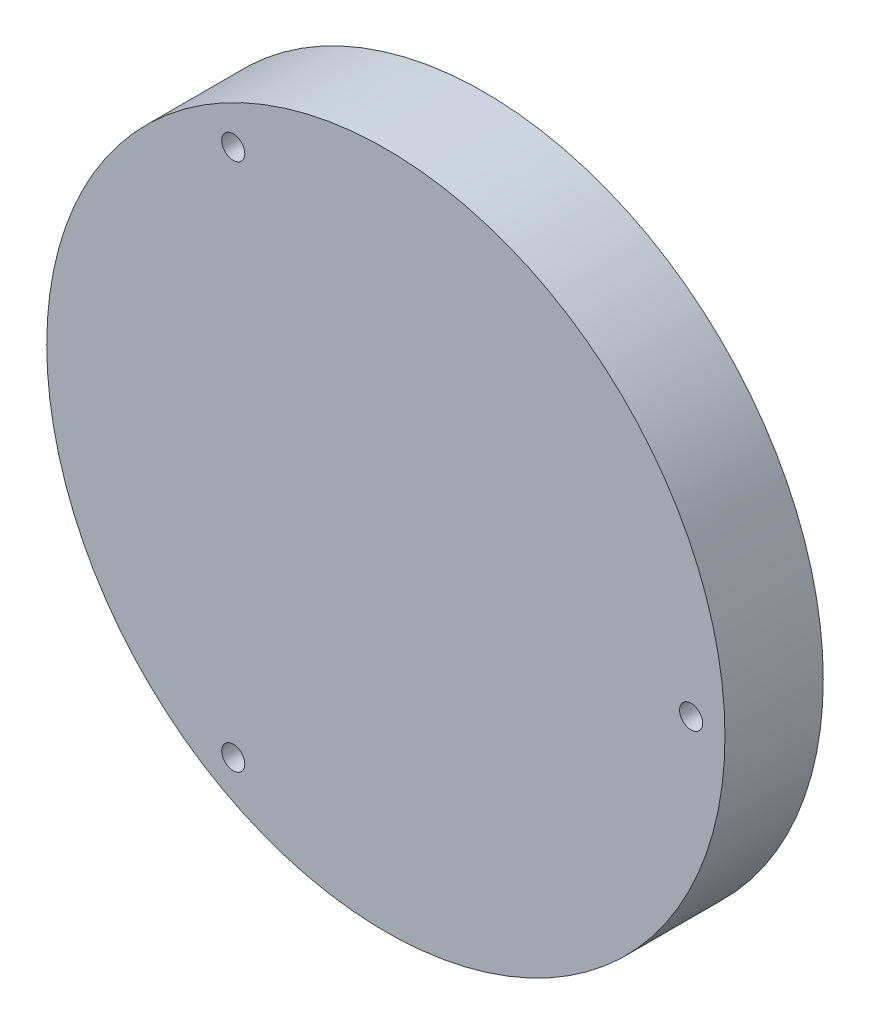
SolidWorks part; units mm, degrees
ref_plane "Front Plane" through (0, 0, 0) normal (1, 0, 0) x (0, 1, 0)
ref_plane "Top Plane" through (0, 0, 0) normal (0, 0, 1) x (0, 1, 0)
ref_plane "Right Plane" through (0, 0, 0) normal (0, 1, 0) x (-1, 0, 0)
sketch "Sketch2" plane through (0, 0, 0) normal (0, 0, 1) x (0, 1, 0)
  line L4 (0, -45) -> (38.9711, 22.5)
  line L5 (38.9711, 22.5) -> (-38.9711, 22.5)
  line L6 (-38.9711, 22.5) -> (0, -45)
  circle A2 centre (0, 0) radius 50
  circle A4 centre (0, 0) radius 22.5 construction
  circle A5 centre (-38.9711, 22.5) radius 1.7
  circle A6 centre (38.9711, 22.5) radius 1.7
  circle A7 centre (0, -45) radius 1.7
  dimension "D1" = 100
  dimension "D2" = 3.4
  dimension "D3" = 3.4
  dimension "D4" = 3.4
  dimension "D5" = 45
extrude "Boss-Extrude1" add sketch "Sketch2" along normal blind 14.4886 contours A2 A7 L6 A5 L5 A6 L4 | A7 L4 A6 L5 A5 L6 region at (0, 0, 0) region at (0, -48.5858, 0)
